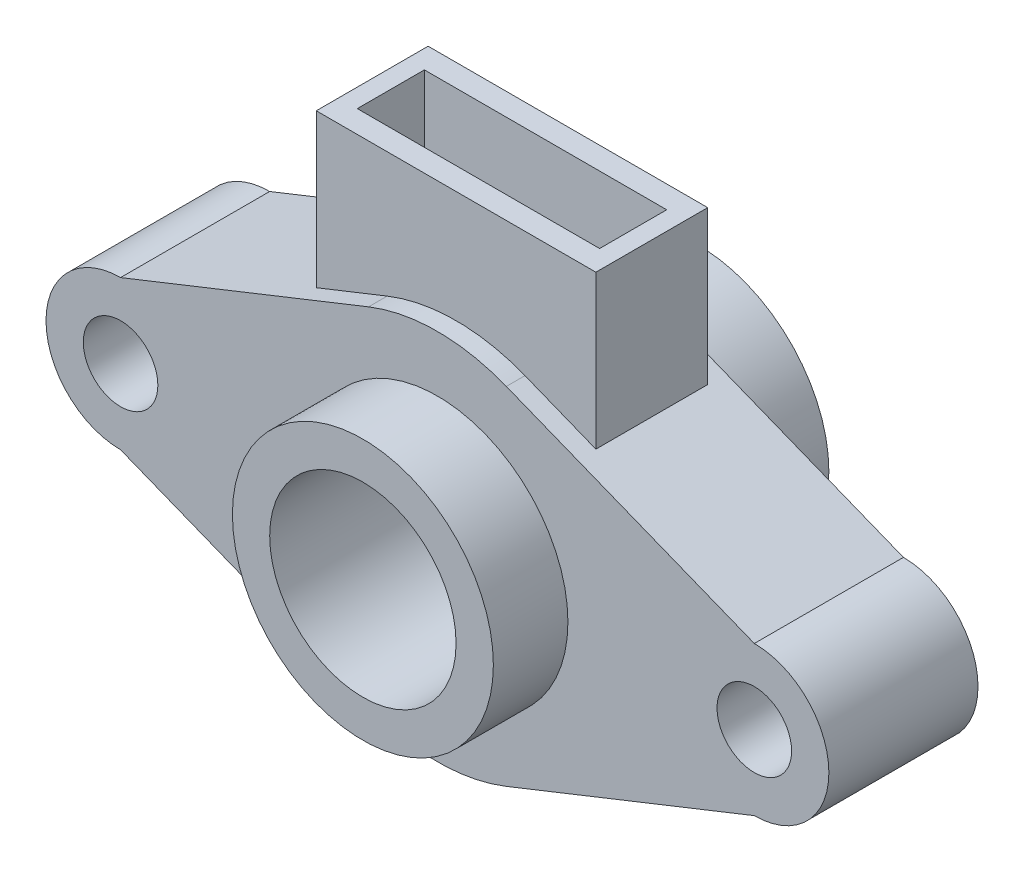
SolidWorks part; units mm, degrees
ref_plane "Front Plane" through (0, 0, 0) normal (0, 0, 1) x (1, 0, 0)
ref_plane "Top Plane" through (0, 0, 0) normal (0, 1, 0) x (1, 0, 0)
ref_plane "Right Plane" through (0, 0, 0) normal (1, 0, 0) x (0, 0, -1)
sketch "Sketch1" plane through (0, 0, 0) normal (0, 0, 1) x (1, 0, 0)
  line L0 (0, 127.8453) -> (0, -133.9819) construction
  line L1 (-236.4626, 0) -> (213.5528, 0) construction
  line L2 (-85, 20) -> (-18.4801, 46.4595)
  line L3 (-85, -20) -> (-18.4801, -46.4595)
  line L4 (85, 20) -> (18.4801, 46.4595)
  line L5 (85, -20) -> (18.4801, -46.4595)
  arc A0 (-18.4801, -46.4595) -> (18.4801, -46.4595) centre (0, 0) ccw
  circle A1 centre (-85, 0) radius 10
  arc A2 (-85, 20) -> (-85, -20) centre (-85, 0) ccw
  arc A3 (85, -20) -> (85, 20) centre (85, 0) ccw
  circle A4 centre (85, 0) radius 10
  arc A5 (18.4801, 46.4595) -> (-18.4801, 46.4595) centre (0, 0) ccw
  dimension "D1" = 100
  dimension "D2" = 40
  dimension "D3" = 20
  dimension "D4" = 20
  dimension "D5" = 40
  dimension "D6" = 170
  dimension "D7" = 85
extrude "Boss-Extrude1" add sketch "Sketch1" along normal mid plane 40
sketch "Sketch2" plane through (0, 0, 20) normal (0, 0, 1) x (1, 0, 0)
  circle A0 centre (0, 0) radius 35
  circle A1 centre (0, 0) radius 25
  dimension "D1" = 50
  dimension "D2" = 70
extrude "Boss-Extrude2" add sketch "Sketch2" along normal blind 20
sketch "Sketch3" plane through (0, 0, -20) normal (0, 0, -1) x (-1, 0, 0)
  circle A0 centre (0, 0) radius 35
  circle A1 centre (0, 0) radius 25
  dimension "D1" = 50
  dimension "D2" = 70
extrude "Boss-Extrude3" add sketch "Sketch3" along normal blind 30
sketch "Sketch4" plane through (0, 0, -20) normal (0, 0, -1) x (-1, 0, 0)
  circle A0 centre (0, 0) radius 25 construction
  circle A1 centre (0, 0) radius 25
extrude "Cut-Extrude1" cut sketch "Sketch4" against normal through all
ref_plane "Plane1" through (0, 80, 0) normal (0, 1, 0) x (1, 0, 0)
sketch "Sketch6" plane through (0, 80, 0) normal (0, 1, 0) x (1, 0, 0)
  line L1 (-37.5, 15) -> (37.5, 15)
  line L2 (-37.5, 15) -> (-37.5, -15)
  line L3 (-37.5, -15) -> (37.5, -15)
  line L4 (37.5, 15) -> (37.5, -15)
  line L5 (-37.5, 15) -> (37.5, -15) construction
  line L6 (-37.5, -15) -> (37.5, 15) construction
  point P0 (0, 0)
  dimension "D1" = 75
  dimension "D2" = 30
extrude "Boss-Extrude6" add sketch "Sketch6" against normal up to surface (46.9281 mm away) up to face at (0, 48.2298, 0)
sketch "Sketch7" plane through (0, 80, 0) normal (0, 1, 0) x (1, 0, 0)
  line L0 (37.5, -15) -> (37.5, 15) construction
  line L1 (-32.5, 9) -> (32.5, 9)
  line L2 (-32.5, 9) -> (-32.5, -9)
  line L3 (-32.5, -9) -> (32.5, -9)
  line L4 (32.5, 9) -> (32.5, -9)
  line L5 (-32.5, 9) -> (32.5, -9) construction
  line L6 (-32.5, -9) -> (32.5, 9) construction
  point P0 (0, 0)
  dimension "D1" = 18
  dimension "D2" = 5
extrude "Cut-Extrude2" cut sketch "Sketch7" against normal blind 40 contours L1 L4 L3 L2
